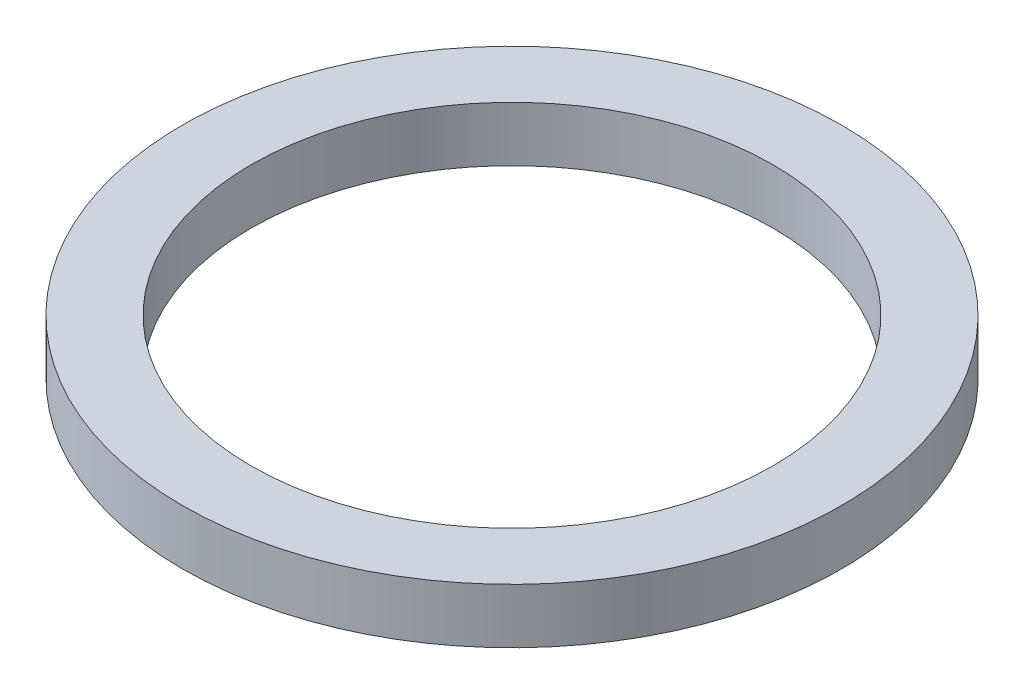
SolidWorks part; units mm, degrees
ref_plane "Front Plane" through (0, 0, 0) normal (0, 0, 1) x (1, 0, 0)
ref_plane "Top Plane" through (0, 0, 0) normal (0, 1, 0) x (1, 0, 0)
ref_plane "Right Plane" through (0, 0, 0) normal (1, 0, 0) x (0, 0, -1)
sketch "Sketch1" plane through (0, 0, 0) normal (0, 1, 0) x (1, 0, 0)
  circle A0 centre (0, 0) radius 60
  dimension "FLANGE_OD" = 120
extrude "Boss-Extrude1" add sketch "Sketch1" along normal blind 10
sketch "Sketch2" plane through (0, 0, 0) normal (0, 1, 0) x (1, 0, 0)
  circle A0 centre (0, 0) radius 47.5
  dimension "BORE_D" = 95
extrude "Cut-Extrude1" cut sketch "Sketch2" along normal through all
sketch "Sketch3" plane through (0, 10, 0) normal (0, 1, 0) x (1, 0, 0)
  circle A0 centre (0, 0) radius 26.0942 construction
  circle A1 centre (-26.0942, 0) radius 1.5292
  dimension "BOLT_D" = 3.0584
  dimension "BOLT_PCD" = 52.1884
extrude "Cut-Extrude2" cut sketch "Sketch3" against normal blind 8.5451 rebuild error yes
pattern_circular "CirPattern1" count 6 over 360 rebuild error yes
